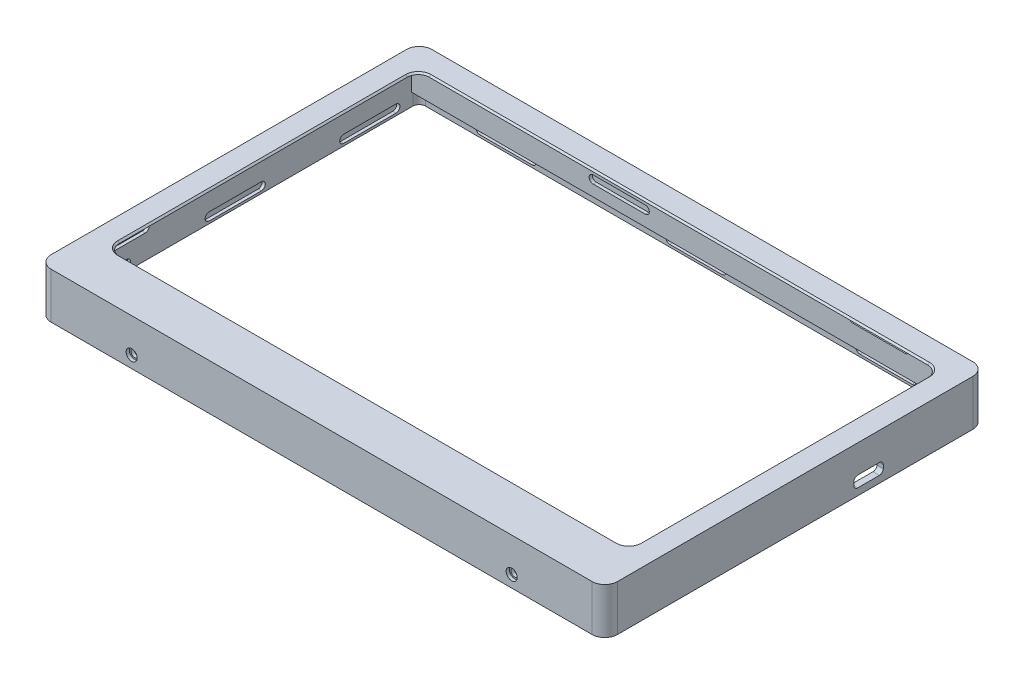
SolidWorks part; units mm, degrees
ref_plane "前基準面" through (0, 0, 0) normal (0, 0, 1) x (1, 0, 0)
ref_plane "上基準面" through (0, 0, 0) normal (0, 1, 0) x (1, 0, 0)
ref_plane "右基準面" through (0, 0, 0) normal (1, 0, 0) x (0, 0, -1)
sketch "草圖1" plane through (0, 0, 0) normal (0, 1, 0) x (1, 0, 0)
  line L1 (-89.4, 60.1) -> (89.4, 60.1)
  line L2 (-89.4, 60.1) -> (-89.4, -60.1)
  line L3 (-89.4, -60.1) -> (89.4, -60.1)
  line L4 (89.4, 60.1) -> (89.4, -60.1)
  line L5 (-89.4, 60.1) -> (89.4, -60.1) construction
  line L6 (-89.4, -60.1) -> (89.4, 60.1) construction
  point P0 (0, 0)
  dimension "D1" = 120.2
  dimension "D2" = 178.8
extrude "填料-伸長1" add sketch "草圖1" along normal blind 16
shell "薄殼1" thickness 2 removed face at (0, 0, 0)
sketch "草圖4" plane through (0, 16, 0) normal (0, 1, 0) x (1, 0, 0)
  line L0 (89.4, 60.1) -> (-89.4, 60.1) construction
  line L1 (-89.4107, 60.1) -> (89.4107, 60.1)
  line L2 (-89.4107, 60.1) -> (-89.4107, -60.1)
  line L3 (-89.4107, -60.1) -> (89.4107, -60.1)
  line L4 (89.4107, 60.1) -> (89.4107, -60.1)
  line L5 (-89.4107, 60.1) -> (89.4107, -60.1) construction
  line L6 (-89.4107, -60.1) -> (89.4107, 60.1) construction
  point P0 (0, 0)
extrude "除料-伸長2" cut sketch "草圖4" against normal blind 1.5
sketch "草圖2" plane through (0, 14.5, 0) normal (0, 1, 0) x (1, 0, 0)
  line L1 (-81.7, 52.1) -> (81.7, 52.1)
  line L2 (-81.7, 52.1) -> (-81.7, -44.82)
  line L3 (-81.7, -44.82) -> (81.7, -44.82)
  line L4 (81.7, 52.1) -> (81.7, -44.82)
  line L5 (-81.7, 52.1) -> (81.7, -44.82) construction
  line L6 (-81.7, -44.82) -> (81.7, 52.1) construction
  line L7 (0, 60.1) -> (0, -60.1) construction
  line L9 (89.4, 60.1) -> (-89.4, 60.1) construction
  line L10 (-89.4, -60.1) -> (89.4, -60.1) construction
  point P0 (0, 3.64)
  dimension "D1" = 8
  dimension "D2" = 163.4
  dimension "D3" = 96.92
extrude "除料-伸長1" cut sketch "草圖2" against normal up to surface (0.5 mm away) up to face at (0, 14, 0)
fillet "圓角2" radius 3 4 edges at (81.7, 14.25, -52.1) (81.7, 14.25, 44.82) (-81.7, 14.25, 44.82) (-81.7, 14.25, -52.1)
chamfer "導角1" distance 1 angle 45 8 edges at (0, 14.5, 44.82) (80.8213, 14.5, 43.9413) (-80.8213, 14.5, 43.9413) (81.7, 14.5, -3.64) (-81.7, 14.5, -3.64) (80.8213, 14.5, -51.2213) (-80.8213, 14.5, -51.2213) (0, 14.5, -52.1)
sketch "草圖13" plane through (0, 14, 0) normal (0, -1, 0) x (1, 0, 0)
  line L1 (-87.4, 58.1) -> (-15, 58.1)
  line L2 (-87.4, 58.1) -> (-87.4, -58.1)
  line L3 (-87.4, -58.1) -> (87.4, -58.1)
  line L4 (87.4, 58.1) -> (87.4, -58.1)
  line L5 (-87.4, 58.1) -> (87.4, -58.1) construction
  line L6 (-87.4, -58.1) -> (87.4, 58.1) construction
  line L8 (87.4, 58.1) -> (87.4, -58.1) construction
  line L9 (87.4, -58.1) -> (-87.4, -58.1) construction
  line L10 (15, 58.1) -> (15, 55.965)
  line L11 (85.325, -55.705) -> (-85.325, -55.705)
  line L12 (85.325, -55.705) -> (85.325, 55.965)
  line L13 (85.325, 55.965) -> (15, 55.965)
  line L14 (-85.325, -55.705) -> (-85.325, 55.965)
  line L15 (85.325, -55.705) -> (-85.325, 55.965) construction
  line L16 (85.325, 55.965) -> (-85.325, -55.705) construction
  line L17 (0, 58.1) -> (0, 55.65) construction
  line L18 (-15, 58.1) -> (-15, 55.965)
  line L19 (15, 58.1) -> (87.4, 58.1)
  line L20 (-15, 55.965) -> (-85.325, 55.965)
  point P0 (0, 0)
  point P24 (0, 0.13)
  dimension "D2" = 170.65
  dimension "D3" = 111.67
  dimension "D4" = 58.23
  dimension "D5" = 15
extrude "填料-伸長2" add sketch "草圖13" along normal blind 1
sketch "Sketch1" plane through (0, 0, -58.1) normal (0, 0, 1) x (1, 0, 0)
  line L0 (-89.4, 14.5) -> (89.4, 14.5)
  line L1 (89.4, 14.5) -> (89.4, 4)
  line L3 (-89.4, 4) -> (-89.4, 14.5)
  line L4 (-89.4, 4) -> (89.4, 4)
  line L5 (89.4, 0) -> (-89.4, 0) construction
  dimension "D1" = 4
extrude "Boss-Extrude1" add sketch "Sketch1" along normal up to surface (2.395 mm away) up to face at (0, 13.5, -55.705)
ref_plane "平面1" through (0, 0, 0) normal (0, 0, 1) x (1, 0, 0)
ref_plane "平面2" through (0, 0, 0) normal (-1, 0, 0) x (0, 0, 1)
fillet "圓角1" radius 4 4 edges at (89.4, 7.25, -60.1) (89.4, 7.25, 60.1) (-89.4, 7.25, 60.1) (-89.4, 7.25, -60.1)
sketch "草圖5" plane through (0, 0, -55.705) normal (0, 0, 1) x (1, 0, 0)
  line L0 (-85.4, 14.5) -> (85.4, 14.5) construction
  line L1 (-11.85, 6.81) -> (-31.85, 6.81)
  line L2 (-11.85, 6.81) -> (-11.85, 10.81)
  line L3 (-11.85, 10.81) -> (-31.85, 10.81)
  line L4 (-31.85, 6.81) -> (-31.85, 10.81)
  line L5 (-31.85, 8.81) -> (-11.85, 8.81) construction
  line L6 (-30.1, 8.81) -> (-13.6, 8.81) construction
  line L7 (-30.1, 10.06) -> (-13.6, 10.06)
  line L8 (-30.1, 7.56) -> (-13.6, 7.56)
  arc A0 (-30.1, 10.06) -> (-30.1, 7.56) centre (-30.1, 8.81) ccw
  arc A1 (-13.6, 7.56) -> (-13.6, 10.06) centre (-13.6, 8.81) ccw
  point P12 (-21.85, 8.81)
  dimension "D1" = 11.85
  dimension "D2" = 3.69
  dimension "D3" = 4
  dimension "D4" = 20
  dimension "D5" = 16.5
  dimension "D6" = 2.5
extrude "除料-伸長3" cut sketch "草圖5" against normal blind 1 contours L8 A1 L7 A0 | L8 A0 L7 A1 region at (-21.85, 8.81, -55.705)
sketch "草圖6" plane through (-87.4, 0, 0) normal (1, 0, 0) x (0, 0, -1)
  line L0 (-56.1, 14.5) -> (56.1, 14.5) construction
  line L1 (-26.64, 6.81) -> (-46.64, 6.81)
  line L2 (-26.64, 6.81) -> (-26.64, 10.81)
  line L3 (-26.64, 10.81) -> (-46.64, 10.81)
  line L4 (-46.64, 6.81) -> (-46.64, 10.81)
  line L5 (-26.64, 8.81) -> (-46.64, 8.81) construction
  line L6 (-28.39, 8.81) -> (-44.89, 8.81) construction
  line L7 (-28.39, 7.56) -> (-44.89, 7.56)
  line L8 (-28.39, 10.06) -> (-44.89, 10.06)
  line L9 (0, 0) -> (0, 14.5) construction
  line L10 (28.39, 11.75) -> (44.89, 11.75) construction
  line L11 (28.39, 10.5) -> (44.89, 10.5)
  line L12 (28.39, 13) -> (44.89, 13)
  arc A0 (-28.39, 7.56) -> (-28.39, 10.06) centre (-28.39, 8.81) ccw
  arc A1 (-44.89, 10.06) -> (-44.89, 7.56) centre (-44.89, 8.81) ccw
  arc A2 (28.39, 10.5) -> (28.39, 13) centre (28.39, 11.75) cw
  arc A3 (44.89, 13) -> (44.89, 10.5) centre (44.89, 11.75) cw
  point P10 (-36.64, 8.81)
  point P20 (36.64, 11.75)
  point P25 (0, 0)
  point P26 (36.64, 8.31)
  point P27 (0, 0)
  dimension "D1" = 3.69
  dimension "D2" = 20
  dimension "D3" = 4
  dimension "D4" = 16.5
  dimension "D5" = 2.5
  dimension "D6" = 26.64
  dimension "D7" = 2.5
  dimension "D8" = 2.75
extrude "除料-伸長4" cut sketch "草圖6" against normal blind 1 contours L8 A1 L7 A0 region at (-87.4, 8.81, 36.64)
extrude "Cut-Extrude1" cut sketch "草圖6<4>" against normal blind 1 contours A3 L12 A2 L11 region at (-87.4, 11.75, -36.64)
sketch "草圖6<4>" plane through (-87.4, 0, 0) normal (1, 0, 0) x (0, 0, -1) same geometry as "草圖6"
mirror "Mirror2" about plane through (0, 0, 0) normal (-1, 0, 0) of "Cut-Extrude1"
sketch "草圖7" plane through (0, 0, 58.1) normal (0, 0, -1) x (-1, 0, 0)
  line L0 (-85.4, 14.5) -> (85.4, 14.5) construction
  line L1 (-57.03, 10.81) -> (-37.03, 10.81)
  line L2 (-57.03, 10.81) -> (-57.03, 6.81)
  line L3 (-57.03, 6.81) -> (-37.03, 6.81)
  line L4 (-37.03, 10.81) -> (-37.03, 6.81)
  line L5 (-57.03, 8.81) -> (-37.03, 8.81) construction
  line L6 (-55.28, 8.81) -> (-38.78, 8.81) construction
  line L7 (-55.28, 10.06) -> (-38.78, 10.06)
  line L8 (-55.28, 7.56) -> (-38.78, 7.56)
  line L9 (0, 0) -> (0, 14.5) construction
  line L10 (-57.03, 10.81) -> (-37.03, 10.81)
  line L11 (-57.03, 6.81) -> (-37.03, 6.81)
  line L12 (57.03, 8.81) -> (37.03, 8.81) construction
  line L13 (57.03, 6.81) -> (37.03, 6.81)
  line L14 (57.03, 10.81) -> (37.03, 10.81)
  line L15 (37.03, 10.81) -> (37.03, 6.81)
  line L16 (57.03, 6.81) -> (37.03, 6.81)
  line L17 (57.03, 10.81) -> (57.03, 6.81)
  line L18 (57.03, 10.81) -> (37.03, 10.81)
  line L19 (55.28, 8.81) -> (38.78, 8.81) construction
  line L20 (55.28, 10.06) -> (38.78, 10.06)
  line L21 (55.28, 7.56) -> (38.78, 7.56)
  arc A0 (-55.28, 10.06) -> (-55.28, 7.56) centre (-55.28, 8.81) ccw
  arc A1 (-38.78, 7.56) -> (-38.78, 10.06) centre (-38.78, 8.81) ccw
  arc A2 (55.28, 10.06) -> (55.28, 7.56) centre (55.28, 8.81) cw
  arc A3 (38.78, 7.56) -> (38.78, 10.06) centre (38.78, 8.81) cw
  point P4 (-37.03, 8.81)
  point P12 (-47.03, 8.81)
  point P27 (47.03, 8.81)
  dimension "D1" = 20
  dimension "D2" = 4
  dimension "D3" = 37.03
  dimension "D4" = 3.69
  dimension "D5" = 16.5
  dimension "D6" = 2.5
extrude "除料-伸長5" cut sketch "草圖7" against normal blind 1 contours L8 A1 L7 A0 | A3 L21 A2 L20 region at (47.03, 8.81, 58.1) region at (-47.03, 8.81, 58.1)
sketch "草圖8" plane through (87.4, 0, 0) normal (-1, 0, 0) x (0, 0, 1)
  line L0 (-56.1, 14.5) -> (56.1, 14.5) construction
  line L1 (43.6, 6.81) -> (53.6, 6.81)
  line L2 (43.6, 6.81) -> (43.6, 10.81)
  line L3 (43.6, 10.81) -> (53.6, 10.81)
  line L4 (53.6, 6.81) -> (53.6, 10.81)
  line L5 (60.1, 14.5) -> (60.1, 0) construction
  line L6 (43.6, 8.81) -> (53.6, 8.81) construction
  line L7 (44.85, 8.81) -> (52.35, 8.81) construction
  line L8 (44.85, 10.06) -> (52.35, 10.06)
  line L9 (44.85, 7.56) -> (52.35, 7.56)
  arc A0 (44.85, 10.06) -> (44.85, 7.56) centre (44.85, 8.81) ccw
  arc A1 (52.35, 7.56) -> (52.35, 10.06) centre (52.35, 8.81) ccw
  point P12 (48.6, 8.81)
  dimension "D1" = 10
  dimension "D2" = 4
  dimension "D3" = 3.69
  dimension "D4" = 6.5
  dimension "D5" = 2.5
  dimension "D6" = 7.5
extrude "除料-伸長6" cut sketch "草圖8" against normal blind 1 contours A1 L8 A0 L9 region at (87.4, 8.81, 48.6)
sketch "草圖9" plane through (89.4, 0, 0) normal (1, 0, 0) x (0, 0, -1)
  line L1 (26.59, 2.18) -> (19.79, 2.18)
  line L2 (27.84, 3.43) -> (27.84, 4.43)
  line L3 (26.59, 5.68) -> (19.79, 5.68)
  line L4 (18.54, 3.43) -> (18.54, 4.43)
  line L5 (27.84, 2.18) -> (18.54, 5.68) construction
  line L6 (27.84, 5.68) -> (18.54, 2.18) construction
  line L8 (60.1, 14.5) -> (60.1, 0) construction
  line L9 (-56.1, 14.5) -> (56.1, 14.5) construction
  arc A0 (19.79, 5.68) -> (18.54, 4.43) centre (19.79, 4.43) ccw
  arc A1 (19.79, 2.18) -> (18.54, 3.43) centre (19.79, 3.43) cw
  arc A2 (26.59, 2.18) -> (27.84, 3.43) centre (26.59, 3.43) ccw
  arc A3 (27.84, 4.43) -> (26.59, 5.68) centre (26.59, 4.43) ccw
  point P0 (23.19, 3.93)
  dimension "D5" = 1.25
  dimension "D1" = 36.91
  dimension "D2" = 10.57
  dimension "D3" = 9.3
  dimension "D4" = 3.5
extrude "除料-伸長7" cut sketch "草圖9" against normal up to next
sketch "草圖10" plane through (89.4, 0, 0) normal (1, 0, 0) x (0, 0, -1)
  line L0 (-60.1, 0) -> (-60.1, 14.5) construction
  line L1 (-40.6, 9.8) -> (-20.6, 9.8)
  line L2 (-40.6, 9.8) -> (-40.6, 3.2)
  line L3 (-40.6, 3.2) -> (-20.6, 3.2)
  line L4 (-20.6, 9.8) -> (-20.6, 3.2)
  line L5 (-40.6, 9.8) -> (-20.6, 3.2) construction
  line L6 (-40.6, 3.2) -> (-20.6, 9.8) construction
  line L7 (-56.1, 14.5) -> (56.1, 14.5) construction
  point P0 (-30.6, 6.5)
  dimension "D1" = 20
  dimension "D2" = 6.6
  dimension "D3" = 19.5
  dimension "D4" = 4.7
extrude "除料-伸長8" [suppressed] cut sketch "草圖10" against normal up to next
sketch "草圖11" plane through (0, 0, -58.1) normal (0, 0, 1) x (1, 0, 0)
  line L0 (-8.25, 2) -> (8.25, 2) construction
  line L1 (-8.25, 3.25) -> (8.25, 3.25)
  line L2 (-8.25, 0.75) -> (8.25, 0.75)
  line L3 (-85.4, 0) -> (85.4, 0) construction
  line L4 (51.75, 2) -> (68.25, 2) construction
  line L5 (51.75, 3.25) -> (68.25, 3.25)
  line L6 (51.75, 0.75) -> (68.25, 0.75)
  line L7 (-68.25, 2) -> (-51.75, 2) construction
  line L8 (-68.25, 3.25) -> (-51.75, 3.25)
  line L9 (-68.25, 0.75) -> (-51.75, 0.75)
  arc A0 (-8.25, 3.25) -> (-8.25, 0.75) centre (-8.25, 2) ccw
  arc A1 (8.25, 0.75) -> (8.25, 3.25) centre (8.25, 2) ccw
  arc A2 (51.75, 3.25) -> (51.75, 0.75) centre (51.75, 2) ccw
  arc A3 (68.25, 0.75) -> (68.25, 3.25) centre (68.25, 2) ccw
  arc A4 (-68.25, 3.25) -> (-68.25, 0.75) centre (-68.25, 2) ccw
  arc A5 (-51.75, 0.75) -> (-51.75, 3.25) centre (-51.75, 2) ccw
  point P2 (0, 2)
  point P8 (0, 0)
  point P13 (60, 2)
  point P20 (-60, 2)
  dimension "D1" = 16.5
  dimension "D2" = 2.5
  dimension "D3" = 2
  dimension "D4" = 2
  dimension "D5" = 2
extrude "除料-伸長9" cut sketch "草圖11" against normal blind 1 contours L2 A1 L1 A0 region at (0, 2, -58.1)
extrude "Cut-Extrude3" cut sketch "草圖11<3>" against normal blind 1 contours L6 A3 L5 A2 | L9 A5 L8 A4 region at (60, 2, -58.1) region at (-60, 2, -58.1)
sketch "草圖11<3>" plane through (0, 0, -58.1) normal (0, 0, 1) x (1, 0, 0) same geometry as "草圖11"
mirror "鏡射1" about plane through (0, 0, 0) normal (0, 0, 1) of "除料-伸長9"
sketch "草圖12" plane through (-87.4, 0, 0) normal (1, 0, 0) x (0, 0, -1)
  line L0 (-8.25, 2) -> (8.25, 2) construction
  line L1 (-8.25, 3.25) -> (8.25, 3.25)
  line L2 (-8.25, 0.75) -> (8.25, 0.75)
  line L3 (-56.1, 0) -> (56.1, 0) construction
  line L4 (34.25, 2) -> (50.75, 2) construction
  line L5 (34.25, 3.25) -> (50.75, 3.25)
  line L6 (34.25, 0.75) -> (50.75, 0.75)
  line L7 (-50.75, 2) -> (-34.25, 2) construction
  line L8 (-50.75, 3.25) -> (-34.25, 3.25)
  line L9 (-50.75, 0.75) -> (-34.25, 0.75)
  arc A0 (-8.25, 3.25) -> (-8.25, 0.75) centre (-8.25, 2) ccw
  arc A1 (8.25, 0.75) -> (8.25, 3.25) centre (8.25, 2) ccw
  arc A2 (34.25, 3.25) -> (34.25, 0.75) centre (34.25, 2) ccw
  arc A3 (50.75, 0.75) -> (50.75, 3.25) centre (50.75, 2) ccw
  arc A4 (-50.75, 3.25) -> (-50.75, 0.75) centre (-50.75, 2) ccw
  arc A5 (-34.25, 0.75) -> (-34.25, 3.25) centre (-34.25, 2) ccw
  point P2 (0, 2)
  point P13 (42.5, 2)
  point P19 (-42.5, 2)
  dimension "D1" = 16.5
  dimension "D2" = 2.5
  dimension "D3" = 2
  dimension "D6" = 42.5
  dimension "D7" = 42.5
  dimension "D4" = 2
  dimension "D5" = 2
extrude "除料-伸長10" cut sketch "草圖12" against normal blind 1
mirror "鏡射2" about plane through (0, 0, 0) normal (-1, 0, 0) of "除料-伸長10"
sketch "Sketch3" plane through (0, 0, -55.705) normal (0, 0, 1) x (1, 0, 0)
  line L0 (51.9003, 11.75) -> (68.4003, 11.75) construction
  line L1 (51.9003, 13) -> (68.4003, 13)
  line L2 (51.9003, 10.5) -> (68.4003, 10.5)
  line L3 (51.75, 2) -> (68.25, 2) construction
  line L5 (85.4, 14.5) -> (-85.4, 14.5) construction
  arc A0 (51.9003, 13) -> (51.9003, 10.5) centre (51.9003, 11.75) ccw
  arc A1 (68.4003, 10.5) -> (68.4003, 13) centre (68.4003, 11.75) ccw
  point P2 (60.1503, 11.75)
  dimension "D1" = 2.5
  dimension "D2" = 2.75
extrude "Cut-Extrude2" cut sketch "Sketch3" against normal blind 1
fillet "Fillet1" radius 2 4 edges at (-87.4, 6.5, 58.1) (87.4, 6.5, 58.1) (-87.4, 2, -58.1) (87.4, 2, -58.1)
sketch "Sketch4" plane through (0, 0, 60.1) normal (0, 0, 1) x (1, 0, 0)
  line L0 (-85.4, 0) -> (85.4, 0) construction
  circle A0 centre (60, 3.75) radius 1.75
  circle A1 centre (60, 3.75) radius 1.25
  dimension "D1" = 3.5
  dimension "D4" = 2.5
  dimension "D2" = 3.75
  dimension "D3" = 60
extrude "Cut-Extrude4" cut sketch "Sketch4" against normal blind 1 contours A1 | A0 A1 region at (58.2995, 3.75, 60.1) region at (60, 3.75, 60.1)
extrude "Cut-Extrude5" cut sketch "Sketch4<3>" against normal up to surface (2 mm away) contours A1 region at (60, 3.75, 60.1) up to face at (0, 2, 58.1)
sketch "Sketch4<3>" plane through (0, 0, 60.1) normal (0, 0, 1) x (1, 0, 0) same geometry as "Sketch4"
mirror "Mirror3" about plane through (0, 0, 0) normal (-1, 0, 0) of "Cut-Extrude5", "Cut-Extrude4"
equation "\"ㄉ\"=4"
equation "\"ㄉ0\"=21"
equation "\"ㄉㄢ\"=21"
